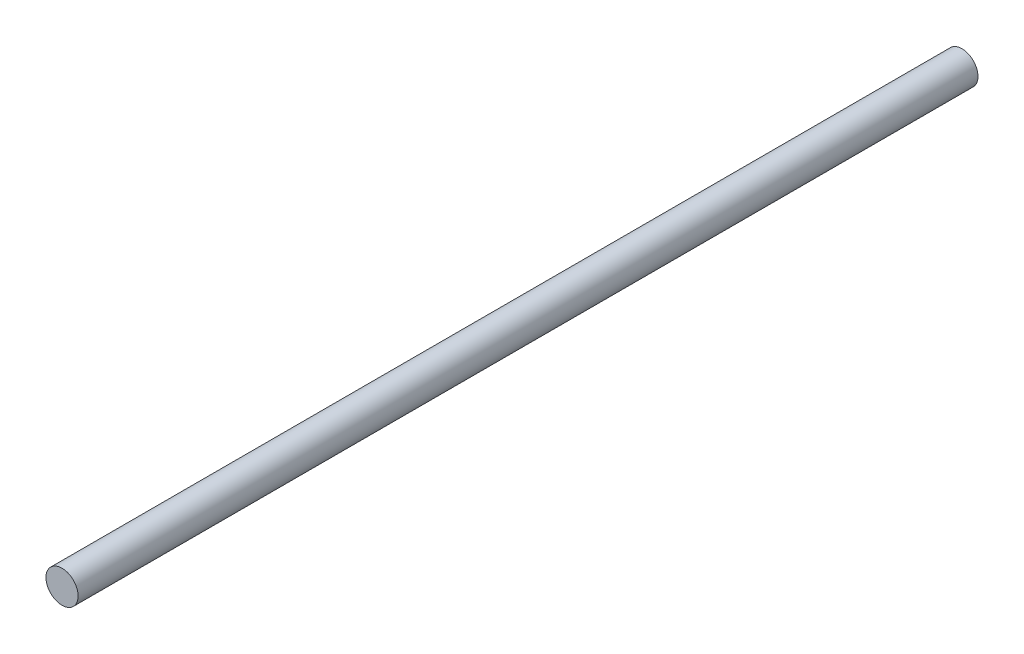
SolidWorks part; units mm, degrees
ref_plane "前基準面" through (0, 0, 0) normal (0, 0, 1) x (1, 0, 0)
ref_plane "上基準面" through (0, 0, 0) normal (0, 1, 0) x (1, 0, 0)
ref_plane "右基準面" through (0, 0, 0) normal (1, 0, 0) x (0, 0, -1)
ref_axis "基準軸1" through (0, -55, 0) along (0, 1, 0)
ref_axis "基準軸2" through (-88.99, 0, 0) along (1, 0, 0)
ref_axis "基準軸3" through (0, 0, 55) along (0, 0, -1)
sketch "草圖1" plane through (0, 0, 0) normal (0, 0, 1) x (1, 0, 0)
  circle A0 centre (0, 0) radius 2.5
  dimension "D1" = 5
extrude "填料-伸長1" add sketch "草圖1" along normal blind 140
